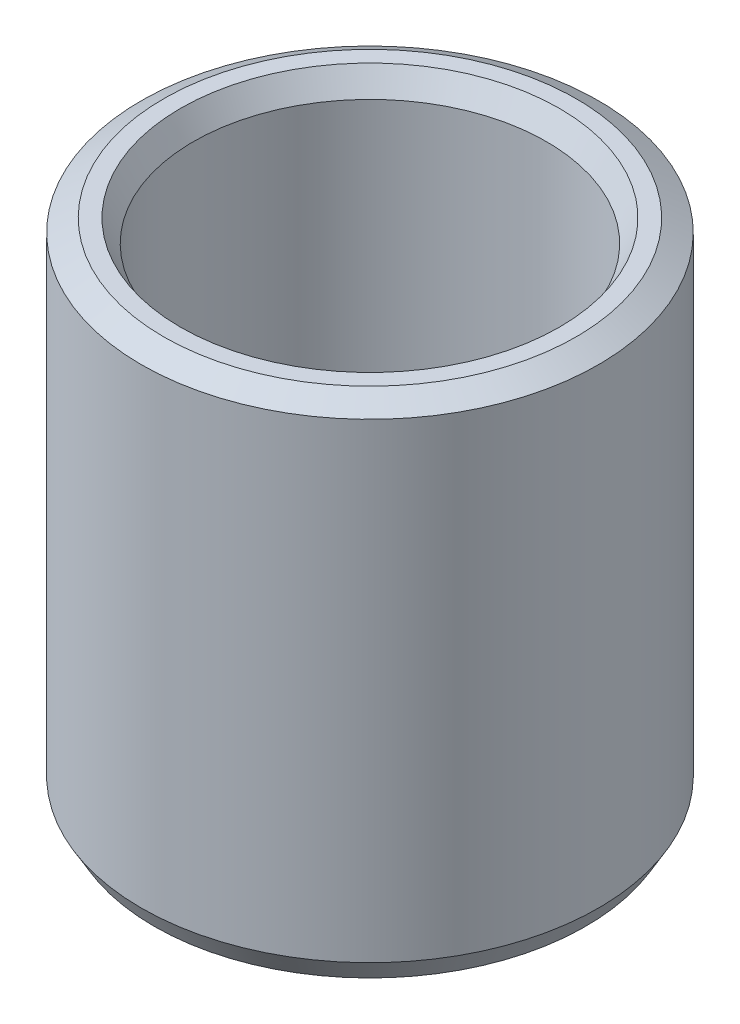
SolidWorks part; units mm, degrees
ref_plane "Front Plane" through (0, 0, 0) normal (0, 0, 1) x (1, 0, 0)
ref_plane "Top Plane" through (0, 0, 0) normal (0, 1, 0) x (1, 0, 0)
ref_plane "Right Plane" through (0, 0, 0) normal (1, 0, 0) x (0, 0, -1)
sketch "Sketch1" plane through (0, 0, 0) normal (0, 1, 0) x (1, 0, 0)
  circle A0 centre (0, 0) radius 50
  dimension "SLEEVE_OD" = 100
extrude "Boss-Extrude1" add sketch "Sketch1" along normal blind 110.6246
sketch "Sketch2" plane through (0, 0, 0) normal (0, 1, 0) x (1, 0, 0)
  circle A0 centre (0, 0) radius 38.6225
  dimension "BORE_D" = 77.2451
extrude "Cut-Extrude1" cut sketch "Sketch2" along normal through all
chamfer "Chamfer1" distance 2.821 angle 60 4 edges at (0, 110.6246, 38.6225) (0, 0, 38.6225) (0, 0, 50) (0, 110.6246, 50) first distance on face at (0, 110.6246, 38.6225) first distance on face at (0, 0, 38.6225) first distance on face at (0, 110.6246, 50)
